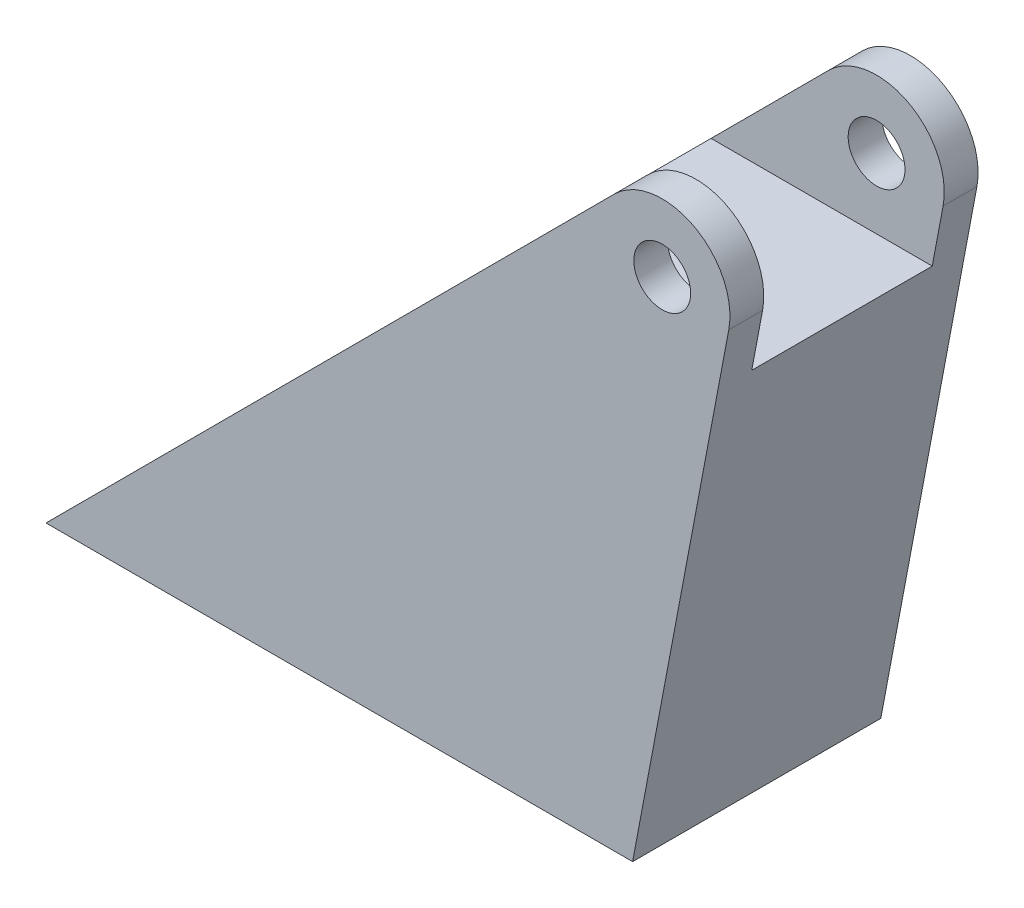
SolidWorks part; units mm, degrees
ref_plane "Front Plane" through (0, 0, 0) normal (0, 0, 1) x (1, 0, 0)
ref_plane "Top Plane" through (0, 0, 0) normal (0, 1, 0) x (1, 0, 0)
ref_plane "Right Plane" through (0, 0, 0) normal (1, 0, 0) x (0, 0, -1)
sketch "Sketch1" plane through (0, 0, 0) normal (0, 0, 1) x (1, 0, 0)
  line L0 (0, 0) -> (0, 19.05)
  line L1 (0, 19.05) -> (13.5255, 90.6215)
  line L2 (-82.55, 0) -> (-82.55, 19.05)
  line L3 (-82.55, 19.05) -> (-2.573, 99.1214)
  line L4 (-82.55, 0) -> (0, 0)
  line L5 (-73.025, 9.525) -> (-92.075, 9.525) construction
  line L6 (-73.025, 9.525) -> (-9.525, 9.525) construction
  line L7 (-92.075, 9.525) -> (-92.075, 391.1122) construction
  line L8 (-92.075, 196.1282) -> (-1.7269, 79.5372) construction
  line L9 (-92.075, 204.1663) -> (4.1661, 92.3902) construction
  circle A0 centre (4.1661, 92.3902) radius 4
  circle A1 centre (-9.525, 9.525) radius 4
  circle A2 centre (-73.025, 9.525) radius 4
  arc A3 (13.5255, 90.6215) -> (-2.573, 99.1214) centre (4.1661, 92.3902) ccw
  circle A4 centre (-92.075, 9.525) radius 127 construction
  circle A5 centre (-92.075, 9.525) radius 114.3 construction
  point P18 (0, 0)
  dimension "D1" = 19.05
  dimension "D10" = 8
  dimension "D7" = 254
  dimension "D8" = 228.6
  dimension "D2" = 9.525
  dimension "D3" = 9.525
  dimension "D4" = 82.55
  dimension "D5" = 19.05
  dimension "D6" = 19.05
  dimension "D9" = 9.525
  dimension "D11" = 147.5
  dimension "D12" = 186.6032
  dimension "D13" = 194.6413
extrude "Boss-Extrude1" add sketch "Sketch1" along normal blind 4.7625
sketch "Sketch2" plane through (0, 0, 4.7625) normal (0, 0, 1) x (1, 0, 0)
  line L0 (-19.1249, 82.55) -> (12.0001, 82.55)
  line L1 (-2.573, 99.1214) -> (-82.55, 19.05) construction
  line L2 (-82.55, 0) -> (0, 0) construction
  line L5 (-2.573, 99.1214) -> (-82.55, 19.05)
  line L6 (-82.55, 19.05) -> (-82.55, 0)
  line L7 (-82.55, 0) -> (0, 0)
  line L8 (0, 0) -> (0, 19.05)
  line L9 (0, 19.05) -> (13.5255, 90.6215)
  line L10 (-19.1249, 82.55) -> (-82.55, 19.05)
  line L11 (-82.55, 19.05) -> (-82.55, 0)
  line L12 (-82.55, 0) -> (0, 0)
  line L13 (0, 0) -> (0, 19.05)
  line L14 (0, 19.05) -> (12.0001, 82.55)
  circle A0 centre (-73.025, 9.525) radius 4 construction
  arc A1 (13.5255, 90.6215) -> (-2.573, 99.1214) centre (4.1661, 92.3902) ccw
  circle A3 centre (-9.525, 9.525) radius 4 construction
  circle A4 centre (-73.025, 9.525) radius 4
  circle A5 centre (-9.525, 9.525) radius 4
  dimension "D2" = 82.55
  dimension "D1" = 0
extrude "Boss-Extrude2" add sketch "Sketch2" along normal blind 25.4
extrude "Boss-Extrude3" add sketch "Sketch1<2>" along normal blind 4.7625 from surface starting at face at (-69.025, 9.525, 30.1625)
sketch "Sketch1<2>" plane through (0, 0, 0) normal (0, 0, 1) x (1, 0, 0) same geometry as "Sketch1"
sketch "Sketch4" plane through (0, 0, 0) normal (0, -1, 0) x (1, 0, 0)
  line L4 (-82.55, 0) -> (0, 0)
  line L5 (0, 0) -> (0, 34.925)
  line L6 (0, 34.925) -> (-82.55, 34.925)
  line L7 (-82.55, 34.925) -> (-82.55, 0)
  line L8 (-82.55, 0) -> (0, 0)
  line L9 (0, 0) -> (0, 34.925)
  line L10 (0, 34.925) -> (-82.55, 34.925)
  line L11 (-82.55, 34.925) -> (-82.55, 0)
  dimension "D1" = 0
extrude "Cut-Extrude1" cut sketch "Sketch4" against normal blind 19.05
sketch "Sketch5" plane through (0, 19.05, 0) normal (0, -1, 0) x (1, 0, 0)
  line L0 (-82.55, 19.05) -> (0, 19.05) construction
  line L1 (-82.55, 34.925) -> (-82.55, 0) construction
  line L2 (0, 34.925) -> (0, 0) construction
  line L3 (-82.55, 0) -> (0, 0) construction
  line L4 (0, 19.05) -> (0, 0) construction
  line L5 (0, 9.525) -> (-82.55, 9.525) construction
  line L6 (0, 28.575) -> (-82.55, 28.575) construction
  line L7 (-73.025, 28.575) -> (-73.025, 9.525) construction
  circle A0 centre (-9.525, 9.525) radius 3.2639
  circle A1 centre (-73.025, 9.525) radius 3.2639
  circle A2 centre (-73.025, 28.575) radius 3.2639
  circle A3 centre (-9.525, 28.575) radius 3.2639
  circle A4 centre (-73.025, 19.05) radius 3.2639
  circle A5 centre (-9.525, 19.05) radius 3.2639
  point P26 (0, 0)
  dimension "D2" = 6.5278
  dimension "D1" = 19.05
  dimension "D3" = 9.525
  dimension "D4" = 63.5
extrude "Cut-Extrude2" cut sketch "Sketch5" against normal blind 31.75
